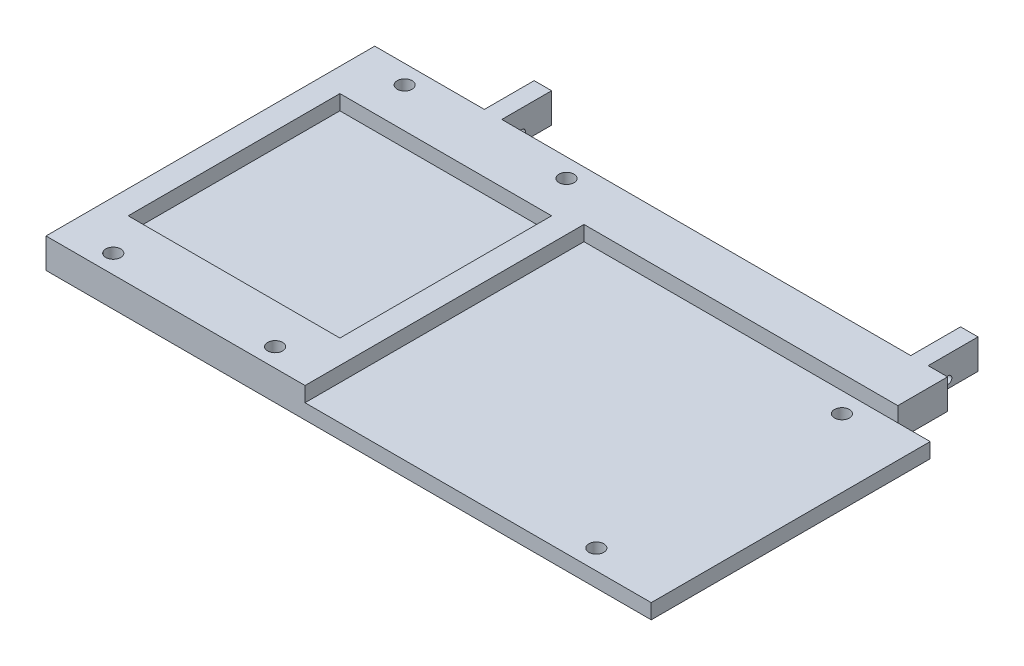
SolidWorks part; units mm, degrees
ref_plane "Front Plane" through (0, 0, 0) normal (0, 0, 1) x (1, 0, 0)
ref_plane "Top Plane" through (0, 0, 0) normal (0, 1, 0) x (1, 0, 0)
ref_plane "Right Plane" through (0, 0, 0) normal (1, 0, 0) x (0, 0, -1)
sketch "Sketch1" plane through (0, 0, 0) normal (0, 1, 0) x (1, 0, 0)
  line L1 (0, 0) -> (-52, 0)
  line L2 (0, 0) -> (0, -66)
  line L3 (0, -66) -> (-52, -66)
  line L4 (-52, 0) -> (-52, -66)
  dimension "D1" = 66
  dimension "D2" = 52
extrude "Boss-Extrude1" add sketch "Sketch1" along normal blind 6
sketch "Sketch2" plane through (0, 6, 0) normal (0, 1, 0) x (1, 0, 0)
  line L0 (-52, 0) -> (-52, -66) construction
  line L1 (-47.25, -11.75) -> (-4.75, -11.75)
  line L2 (-47.25, -11.75) -> (-47.25, -54.25)
  line L3 (-47.25, -54.25) -> (-4.75, -54.25)
  line L4 (-4.75, -11.75) -> (-4.75, -54.25)
  line L5 (-52, -66) -> (0, -66) construction
  point P6 (-47.25, -33)
  point P7 (-52, -33)
  point P8 (-26, -54.25)
  point P11 (-26, -66)
  dimension "D1" = 42.5
  dimension "D2" = 42.5
  dimension "D3" = 0
  dimension "D4" = 0
extrude "Cut-Extrude1" cut sketch "Sketch2" against normal blind 3
sketch "Sketch3" plane through (0, 6, 0) normal (0, 1, 0) x (1, 0, 0)
  line L0 (-4.75, -11.75) -> (-47.25, -11.75) construction
  line L1 (-47.25, -11.75) -> (-47.25, -54.25) construction
  line L2 (-26, 0) -> (-26, -78.9032) construction
  line L3 (0, 0) -> (-52, 0) construction
  line L4 (-52, -33) -> (19.2006, -33) construction
  line L5 (-52, 0) -> (-52, -66) construction
  circle A0 centre (-42.25, -3.75) radius 1.5
  circle A1 centre (-9.75, -3.75) radius 1.5
  circle A2 centre (-9.75, -62.25) radius 1.5
  circle A3 centre (-42.25, -62.25) radius 1.5
  dimension "D1" = 8
  dimension "D2" = 3
  dimension "D3" = 5
extrude "Cut-Extrude2" cut sketch "Sketch3" against normal blind 13
sketch "Sketch4" plane through (0, 0, 0) normal (1, 0, 0) x (0, 0, -1)
  line L0 (-66, 6) -> (0, 6) construction
  line L1 (0, 0) -> (-10, 0)
  line L2 (0, 0) -> (0, 6)
  line L3 (0, 6) -> (-10, 6)
  line L4 (-10, 0) -> (-10, 6)
  dimension "D1" = 10
extrude "Boss-Extrude2" add sketch "Sketch4" along normal blind 63
sketch "Sketch5" plane through (0, 0, 0) normal (0, 0, -1) x (-1, 0, 0)
  line L0 (-63, 6) -> (52, 6) construction
  line L1 (30, 6) -> (26.5, 6)
  line L2 (30, 6) -> (30, 0)
  line L3 (30, 0) -> (26.5, 0)
  line L4 (26.5, 6) -> (26.5, 0)
  line L5 (-63, 0) -> (52, 0) construction
  line L6 (52, 6) -> (52, 0) construction
  line L8 (-55.6, 6) -> (-59.1, 6)
  line L9 (-55.6, 6) -> (-55.6, 0)
  line L10 (-55.6, 0) -> (-59.1, 0)
  line L11 (-59.1, 6) -> (-59.1, 0)
  point P14 (-57.35, 0)
  point P15 (28.25, 0)
  dimension "D1" = 3.5
  dimension "D2" = 22
  dimension "D3" = 3.5
  dimension "D4" = 85.6
extrude "Boss-Extrude3" add sketch "Sketch5" along normal blind 10
sketch "Sketch6" plane through (59.1, 0, 0) normal (1, 0, 0) x (0, 0, -1)
  line L0 (10, 0) -> (0, 0) construction
  line L1 (0, 6) -> (0, 0) construction
  circle A0 centre (4, 1.5) radius 0.75
  dimension "D1" = 1.5
  dimension "D2" = 4
  dimension "D3" = 1.5
extrude "Cut-Extrude3" cut sketch "Sketch6" against normal blind 114
sketch "Sketch7" plane through (0, 0, 0) normal (0, -1, 0) x (-1, 0, 0)
  line L0 (52, -66) -> (0, -66) construction
  line L1 (0, -10) -> (-69.5, -10)
  line L2 (0, -10) -> (0, -66)
  line L3 (0, -66) -> (-69.5, -66)
  line L4 (-69.5, -10) -> (-69.5, -66)
  circle A2 centre (-55.8, -14.018) radius 1.5
  circle A4 centre (-54.5, -62.018) radius 1.5
  dimension "D3" = 56
  dimension "D4" = 15
  dimension "D5" = 13.7
  dimension "D6" = 3
  dimension "D7" = 48
  dimension "D8" = 3
  dimension "D1" = 0
  dimension "D2" = 69.5
extrude "Boss-Extrude4" add sketch "Sketch7" against normal blind 3
